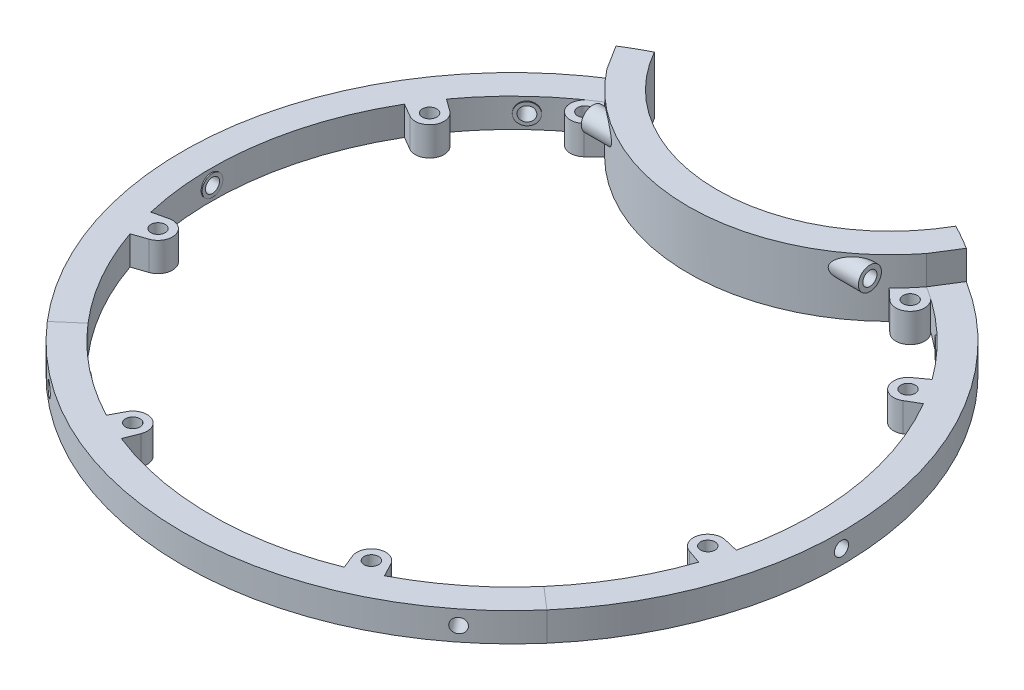
SolidWorks part; units mm, degrees
note: The reader was unsure of these and kept them because the rebuilt part matched: shared geometry of "Sketch9<3>", "Sketch1<4>", "Sketch12<4>", "Sketch13<6>", "Sketch14<8>".
ref_plane "Front Plane" through (0, 0, 0) normal (0, 0, 1) x (1, 0, 0)
ref_plane "Top Plane" through (0, 0, 0) normal (0, 1, 0) x (1, 0, 0)
ref_plane "Right Plane" through (0, 0, 0) normal (1, 0, 0) x (0, 0, -1)
sketch "Sketch1" plane through (0, 0, 0) normal (0, 1, 0) x (1, 0, 0)
  line L0 (-33.1606, 64.4719) -> (0, 83.2333) construction
  line L1 (0, 83.2333) -> (33.1606, 64.4719) construction
  line L2 (-33.1606, 64.4719) -> (33.1606, 64.4719) construction
  line L3 (38.5317, 61.413) -> (35.1569, 56.0341)
  line L4 (0, 0) -> (0, -18.8616) construction
  line L5 (-38.5317, 61.413) -> (-35.1569, 56.0341)
  line L6 (54.9634, -47.2787) -> (50.1493, -43.1378)
  circle A0 centre (0, 0) radius 72.5
  circle A1 centre (0, 83.2333) radius 38.1
  arc A2 (-35.1569, 56.0341) -> (35.1569, 56.0341) centre (0, 0) ccw
  arc A3 (-35.1569, 56.0341) -> (35.1569, 56.0341) centre (0, 83.2333) ccw
  circle A4 centre (0, 0) radius 66.15 construction
  circle A5 centre (0, 83.2333) radius 44.45 construction
  point P12 (50.8, 83.2333)
  dimension "D1" = 145
  dimension "D2" = 76.2
  dimension "D3" = 121
  dimension "D6" = 295.79
  dimension "D7" = 98.597
  dimension "D4" = 6.35
  dimension "D5" = 6.35
extrude "Boss-Extrude1" add sketch "Sketch1" along normal blind 12.7
sketch "Sketch9" plane through (0, 0, 0) normal (1, 0, 0) x (0, 0, -1)
  circle A0 centre (48.26, 9.525) radius 2.54
  circle A1 centre (48.26, 9.525) radius 1.55
  dimension "D1" = 9.525
  dimension "D2" = 3.1
  dimension "D3" = 5.08
  dimension "D4" = 48.26
extrude "Cut-Extrude2" cut sketch "Sketch9" against normal up to next contours A1
extrude "Boss-Extrude3" add sketch "Sketch9<3>" against normal blind 7.62 from offset 22.86 contours A0 A1 offset against normal yes
sketch "Sketch9<3>" plane through (0, 0, 0) normal (1, 0, 0) x (0, 0, -1) same geometry as "Sketch9"
mirror "Mirror1" about plane through (0, 0, 0) normal (1, 0, 0) of "Cut-Extrude2", "Boss-Extrude3"
extrude "Boss-Extrude4" add sketch "Sketch1<4>" along normal blind 6.35 separate body contours A2 L6 A0 L3
sketch "Sketch1<4>" plane through (0, 0, 0) normal (0, 1, 0) x (1, 0, 0) same geometry as "Sketch1"
sketch "Sketch10" plane through (0, 6.35, 0) normal (0, 1, 0) x (1, 0, 0)
  line L0 (50.756, 37.0634) -> (53.4227, 39.0107)
  line L1 (54.2329, 31.7595) -> (57.0823, 33.4281)
  line L2 (0, 0) -> (65.4068, 9.888) construction
  line L3 (61.1974, -14.3091) -> (64.4127, -15.0609)
  line L4 (59.4437, -20.4038) -> (62.5669, -21.4758)
  line L5 (0, 0) -> (52.6284, 34.4993) construction
  line L6 (0, 0) -> (35.1569, 56.0341) construction
  circle A0 centre (52.6284, 34.4993) radius 1.5875
  circle A1 centre (52.6284, 34.4993) radius 3.175
  arc A2 (50.1493, -43.1378) -> (35.1569, 56.0341) centre (0, 0) ccw construction
  circle A3 centre (60.4745, -17.4008) radius 3.175
  circle A4 centre (60.4745, -17.4008) radius 1.5875
  arc M6 (35.1569, 56.0341) -> (50.1493, -43.1378) centre (0, 0) cw
  dimension "D1" = 6.35
  dimension "D5" = 3.175
  dimension "D2" = 3.302
  dimension "D3" = 49.298
  dimension "D4" = 24.649
extrude "Boss-Extrude5" add sketch "Sketch10" against normal blind 6.35 contours A1 L1 L0 M6 | A1 A0 | A3 A4 | L3 A3 L4 M6
pattern_circular "CirPattern3" count 2 every 98.597 about axis through (0, 0, 0) along (0, 1, 0) of bodies 112
sketch "Sketch11" plane through (0, 0, 0) normal (0, 1, 0) x (1, 0, 0)
  line L0 (0, 0) -> (45.1003, 48.392) construction
  line L1 (0, 0) -> (66.15, 0) construction
  line L2 (0, 0) -> (41.1068, -51.8271) construction
  line L3 (0, 0) -> (0, 22.5696) construction
  line L4 (0, 0) -> (-41.1068, -51.8271) construction
  arc A0 (53.4227, 39.0107) -> (35.1569, 56.0341) centre (0, 0) ccw construction
  arc A1 (64.4127, -15.0609) -> (57.0823, 33.4281) centre (0, 0) ccw construction
  arc A2 (30.5869, -58.6538) -> (50.1493, -43.1377) centre (0, 0) ccw construction
  arc A3 (-50.1493, -43.1378) -> (-30.5869, -58.6538) centre (0, 0) ccw construction
ref_plane "Plane1" through (45.1003, 0, -48.392) normal (-0.6818, 0, 0.7315) x (0.7315, 0, 0.6818)
sketch "Sketch12" plane through (45.1003, 0, -48.392) normal (-0.6818, 0, 0.7315) x (0.7315, 0, 0.6818)
  circle A0 centre (0, 3.175) radius 2.286
  circle A1 centre (0, 3.175) radius 1.55
  point P3 (0, 0)
  dimension "D1" = 4.572
  dimension "D2" = 3.1
  dimension "D3" = 3.175
extrude "Cut-Extrude3" cut sketch "Sketch12" against normal through all and the other way up to next contours A1
extrude "Boss-Extrude6" add sketch "Sketch12<4>" along normal blind 0.254
sketch "Sketch12<4>" plane through (45.1003, 0, -48.392) normal (-0.6818, 0, 0.7315) x (0.7315, 0, 0.6818) same geometry as "Sketch12"
ref_plane "Plane2" through (66.15, 0, 0) normal (-1, 0, 0) x (0, 0, 1)
sketch "Sketch13" plane through (66.15, 0, 0) normal (-1, 0, 0) x (0, 0, 1)
  circle A0 centre (0, 3.175) radius 2.286
  circle A1 centre (0, 3.175) radius 1.55
  point P3 (0, 0)
  dimension "D1" = 4.572
  dimension "D2" = 3.1
extrude "Cut-Extrude4" cut sketch "Sketch13" against normal through all and the other way up to next contours A1
extrude "Boss-Extrude7" add sketch "Sketch13<6>" along normal blind 0.254
sketch "Sketch13<6>" plane through (66.15, 0, 0) normal (-1, 0, 0) x (0, 0, 1) same geometry as "Sketch13"
ref_plane "Plane3" through (41.1068, 0, 51.8271) normal (-0.6214, 0, -0.7835) x (-0.7835, 0, 0.6214)
sketch "Sketch14" plane through (41.1068, 0, 51.8271) normal (-0.6214, 0, -0.7835) x (-0.7835, 0, 0.6214)
  circle A0 centre (0, 3.175) radius 2.286
  circle A1 centre (0, 3.175) radius 1.55
  point P3 (0, 0)
  dimension "D1" = 4.572
  dimension "D2" = 3.1
extrude "Cut-Extrude5" cut sketch "Sketch14" against normal through all and the other way up to next contours A1
extrude "Boss-Extrude8" add sketch "Sketch14<8>" along normal blind 0.254
sketch "Sketch14<8>" plane through (41.1068, 0, 51.8271) normal (-0.6214, 0, -0.7835) x (-0.7835, 0, 0.6214) same geometry as "Sketch14"
mirror "Mirror11" about plane through (0, 0, 0) normal (1, 0, 0) of bodies 118
mirror "Mirror12" about plane through (0, 0, 0) normal (1, 0, 0) of "Boss-Extrude8", "Cut-Extrude5"
sketch "Sketch15" plane through (0, 0, 0) normal (0, 1, 0) x (1, 0, 0)
  line L0 (-31.305, 51.677) -> (-33.6161, 49.5027)
  line L1 (-31.305, 51.677) -> (-33.4055, 53.9097) construction
  circle A0 centre (-35.7917, 51.8151) radius 3.175
  circle A1 centre (-35.7917, 51.8151) radius 1.5875
  circle A2 centre (-52.6284, 34.4993) radius 1.5875 construction
  arc A3 (-35.1569, 56.0341) -> (35.1569, 56.0341) centre (0, 83.2333) ccw construction
  arc A4 (-35.1569, 56.0341) -> (-53.4227, 39.0107) centre (0, 0) ccw construction
  arc A5 (-54.2329, 31.7595) -> (-50.756, 37.0634) centre (-52.6284, 34.4993) ccw construction
  arc A6 (-35.1569, 56.0341) -> (-37.5962, 54.4275) centre (0, 0) ccw
  arc A7 (-35.1569, 56.0341) -> (-33.4055, 53.9097) centre (0, 83.2333) ccw
  arc A8 (-35.1569, 56.0341) -> (-31.305, 51.677) centre (0, 83.2333) ccw
extrude "Boss-Extrude9" add sketch "Sketch15" along normal blind 6.35 contours A7 A6 A0 | A0 A1 | A8 A0 L0
mirror "Mirror13" about plane through (0, 0, 0) normal (1, 0, 0) of "Boss-Extrude9"
equation "\"D7@Sketch1\"=\"D6@Sketch1\"/3"
equation "\"D4@Sketch10\"=\"D3@Sketch10\"/2"
equation "\"D2@CirPattern3\"=295.79/3"
